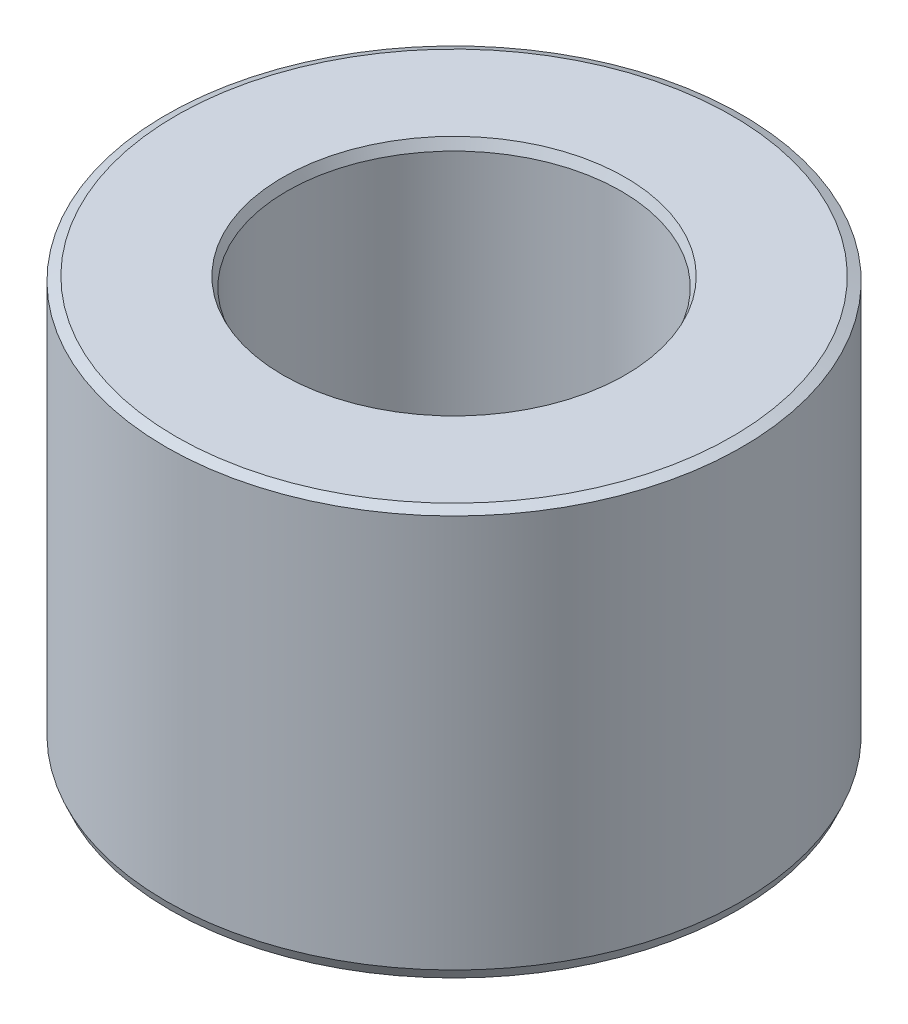
SolidWorks part; units mm, degrees
ref_plane "Front Plane" through (0, 0, 0) normal (0, 0, 1) x (1, 0, 0)
ref_plane "Top Plane" through (0, 0, 0) normal (0, 1, 0) x (1, 0, 0)
ref_plane "Right Plane" through (0, 0, 0) normal (1, 0, 0) x (0, 0, -1)
sketch "Sketch1" plane through (0, 0, 0) normal (0, 1, 0) x (1, 0, 0)
  circle A0 centre (0, 0) radius 35
  dimension "SLEEVE_OD" = 70
extrude "Boss-Extrude1" add sketch "Sketch1" along normal blind 49.508
sketch "Sketch2" plane through (0, 0, 0) normal (0, 1, 0) x (1, 0, 0)
  circle A0 centre (0, 0) radius 20.3127
  dimension "BORE_D" = 40.6253
extrude "Cut-Extrude1" cut sketch "Sketch2" along normal through all
chamfer "Chamfer1" distance 0.5084 angle 66.944 4 edges at (0, 49.508, 20.3127) (0, 0, 20.3127) (0, 0, 35) (0, 49.508, 35) first distance on face at (0, 49.508, 20.3127) first distance on face at (0, 0, 20.3127) first distance on face at (0, 49.508, 35)
